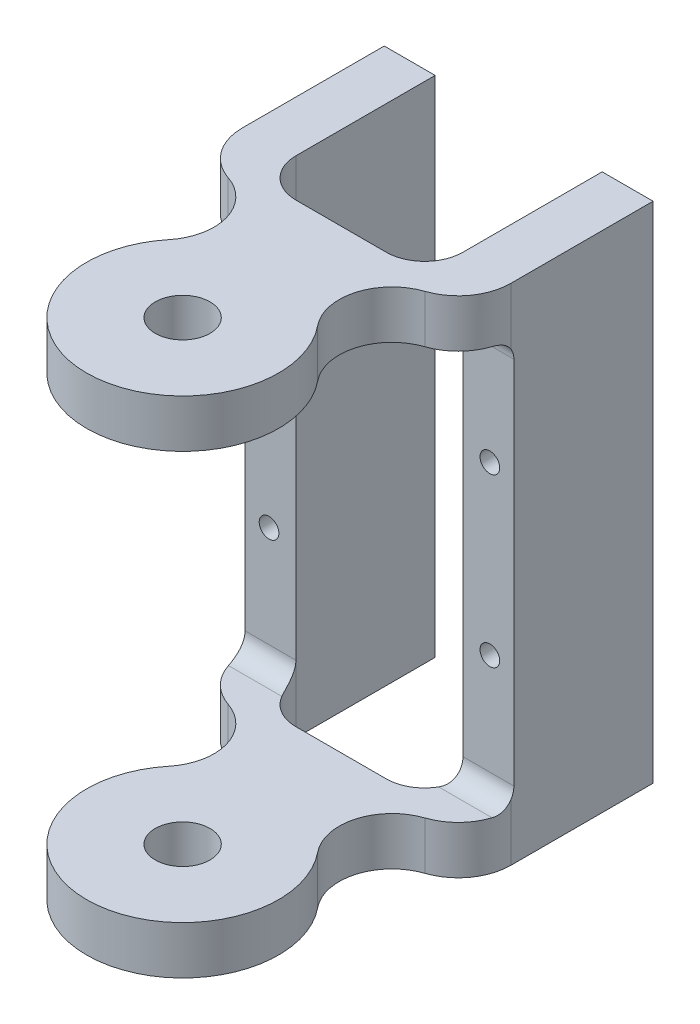
SolidWorks part; units mm, degrees
material "7075-T6 (SN)"
ref_plane "Face" through (0, 0, 0) normal (0, 0, 1) x (1, 0, 0)
ref_plane "Dessus" through (0, 0, 0) normal (0, 1, 0) x (1, 0, 0)
ref_plane "Droite" through (0, 0, 0) normal (1, 0, 0) x (0, 0, -1)
sketch "Esquisse3" plane through (0, 0, 0) normal (0, 1, 0) x (1, 0, 0)
  line L0 (-14, 0) -> (-14, -35)
  line L1 (0, 0) -> (0, -35) construction
  line L3 (14, -35) -> (14, 0)
  line L4 (-14, 0) -> (14, 0)
  line L6 (-14, 0) -> (-14, 3.841) construction
  line L7 (14, 0) -> (14, 6.0564) construction
  circle A0 centre (0, -35) radius 2.85
  arc A1 (-14, -35) -> (14, -35) centre (0, -35) ccw
  dimension "D2" = 5.7
  dimension "D1" = 28
  dimension "D4" = 35
extrude "Boss.-Extru.1" add sketch "Esquisse3" along normal mid plane 52.5
sketch "Esquisse5" plane through (0, 0, 0) normal (1, 0, 0) x (0, 0, -1)
  line L1 (-49, 21.25) -> (-24.5, 21.25)
  line L6 (-24.5, 21.25) -> (-24.5, -21.25)
  line L7 (-24.5, -21.25) -> (-49, -21.25)
  line L8 (-49, 26.25) -> (-49, -26.25) construction
  line L9 (-49, -21.25) -> (-49, 21.25)
  line L10 (-35, 26.25) -> (-49, 26.25) construction
  line L11 (-49, -26.25) -> (-35, -26.25) construction
  dimension "D1" = 5
  dimension "D2" = 5
  dimension "D3" = 24.5
extrude "Enlèv. mat.-Extru.2" cut sketch "Esquisse5" against normal through all and the other way through all
sketch "Esquisse6" plane through (0, -26.25, 0) normal (0, 1, 0) x (1, 0, 0)
  line L0 (-9, 0) -> (-9, -18) construction
  line L1 (-9, -18) -> (9, -18) construction
  line L2 (-8.7, 0) -> (-8.7, -14.5)
  line L5 (-4.7, -18.5) -> (4.7, -18.5)
  line L7 (14, -35) -> (14, 0) construction
  line L8 (9, -18) -> (9, 0) construction
  line L9 (9, 0) -> (-9, 0) construction
  line L11 (0, 0) -> (0, -37) construction
  line L12 (0, -35) -> (14, -26.9171) construction
  line L13 (-14, 0) -> (-14, -35) construction
  line L14 (8.7, -14.5) -> (8.7, 0)
  line L15 (14, 0) -> (-14, 0) construction
  line L16 (8.7, 0) -> (-8.7, 0)
  arc A0 (-8.7, -14.5) -> (-4.7, -18.5) centre (-4.7, -14.5) ccw
  arc A1 (4.7, -18.5) -> (8.7, -14.5) centre (4.7, -14.5) ccw
  point P4 (0, -18.5)
  dimension "D1" = 18
  dimension "D2" = 4
  dimension "D6" = 5.3
  dimension "D8" = 18.5
extrude "Enlèv. mat.-Extru.3" cut sketch "Esquisse6" against normal through all and the other way through all
sketch "Esquisse11" plane through (0, -26.25, 0) normal (0, -1, 0) x (1, 0, 0)
  line L0 (0, 49) -> (0, 14.7927) construction
  line L1 (-14, 0) -> (-14, 35) construction
  line L3 (14, 14.7927) -> (14, 35)
  line L4 (14, 35) -> (14, 0) construction
  line L5 (-14, 14.7927) -> (14, 14.7927) construction
  line L6 (-14, 14.7927) -> (-14, 35)
  arc A0 (7.7551, 28.6866) -> (-7.7551, 28.6866) centre (0, 35) ccw
  arc A1 (-10.2602, 20.0035) -> (-14, 14.7927) centre (-8.5, 14.7927) ccw
  arc A2 (7.7551, 28.6866) -> (10.2602, 20.0035) centre (12.0203, 25.2142) ccw
  arc A3 (14, 35) -> (-14, 35) centre (0, 35) ccw construction
  arc A4 (14, 35) -> (-14, 35) centre (0, 35) ccw
  arc A5 (-7.7551, 28.6866) -> (-10.2602, 20.0035) centre (-12.0203, 25.2142) cw
  arc A6 (10.2602, 20.0035) -> (14, 14.7927) centre (8.5, 14.7927) cw
  dimension "D1" = 20
  dimension "D2" = 5.5
extrude "Enlèv. mat.-Extru.6" cut sketch "Esquisse11" against normal through all
ref_plane "Plan1" through (0, 0, 45) normal (0, 0, 1) x (1, 0, 0)
sketch "Esquisse16" plane through (0, 0, 0) normal (0, 0, -1) x (-1, 0, 0)
  line L0 (0, 23.0718) -> (0, -4.4703) construction
  line L4 (-17.4288, 0) -> (26.647, 0) construction
  circle A0 centre (-11.5, 8.7) radius 1.025
  circle A1 centre (11.5, 8.7) radius 1.025
  circle A2 centre (-11.5, -8.7) radius 1.025
  circle A3 centre (11.5, -8.7) radius 1.025
  dimension "D2" = 8.7
  dimension "D3" = 2.05
  dimension "D4" = 2.05
  dimension "D5" = 2.05
  dimension "D6" = 2.05
  dimension "D7" = 17.4
  dimension "D8" = 8.7
  dimension "D1" = 17.4
  dimension "D9" = 23
  dimension "D10" = 23
  dimension "D11" = 11.5
extrude "Enlèv. mat.-Extru.7" cut sketch "Esquisse16" against normal through all
sketch "Esquisse19" plane through (0, 0, 24.5) normal (0, 0, 1) x (1, 0, 0)
  line L0 (-6.5669, -21.25) -> (6.5669, -21.25) construction
  line L1 (-15, 21.25) -> (15, 21.25)
  line L2 (-15, 21.25) -> (-15, -21.25)
  line L3 (-15, -21.25) -> (15, -21.25)
  line L4 (15, 21.25) -> (15, -21.25)
  line L5 (-6.5669, 21.25) -> (6.5669, 21.25) construction
  line L6 (0, 10.4807) -> (0, -9.59) construction
  dimension "D1" = 30
  dimension "D2" = 15
extrude "Enlèv. mat.-Extru.11" cut sketch "Esquisse19" against normal blind 10
fillet "Congé1" radius 2 4 edges at (11.35, -21.25, 14.5) (-11.35, -21.25, 14.5) (11.35, 21.25, 14.5) (-11.35, 21.25, 14.5)
